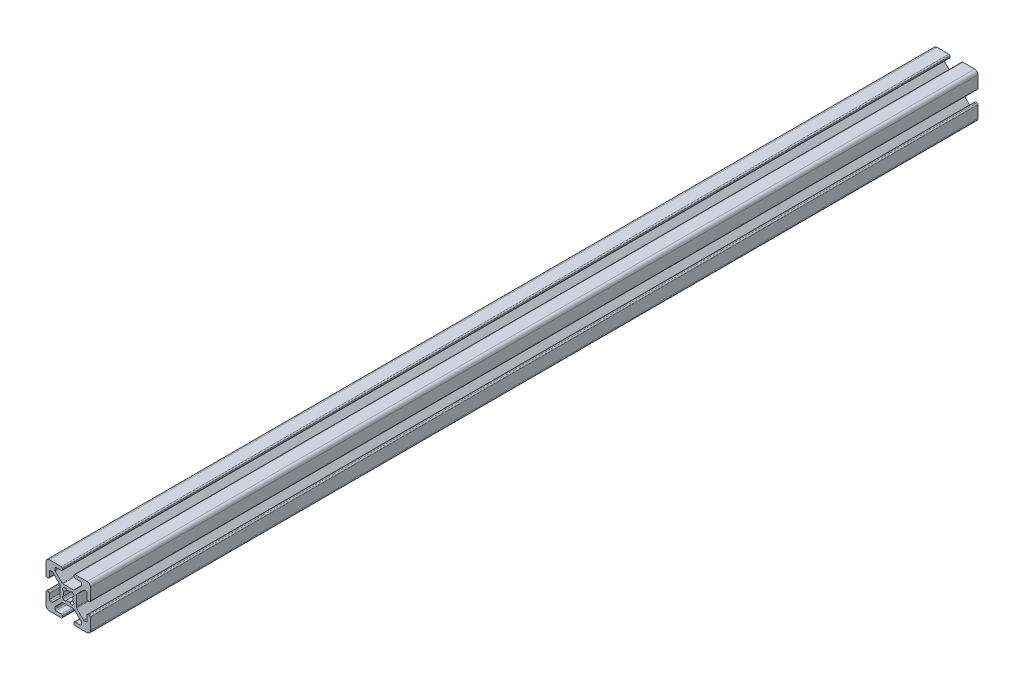
SolidWorks part; units mm, degrees
ref_plane "Front Plane" through (0, 0, 0) normal (0, 0, 1) x (1, 0, 0)
ref_plane "Top Plane" through (0, 0, 0) normal (0, 1, 0) x (1, 0, 0)
ref_plane "Right Plane" through (0, 0, 0) normal (1, 0, 0) x (0, 0, -1)
sketch "Sketch1" plane through (0, 0, 0) normal (0, 0, 1) x (1, 0, 0)
  line L0 (-5.0323, -0.3411) -> (-5.5163, -0.3411)
  line L1 (-6.0243, 0.1669) -> (-6.0243, 2.5159)
  line L2 (-4.5243, 0.1669) -> (-4.5243, 5.5289)
  line L3 (-10.8693, -5.355) -> (-10.8693, -0.5871)
  line L4 (-7.2582, 3.0239) -> (-6.5323, 3.0239)
  line L5 (-7.6174, 2.8752) -> (-10.7205, -0.2279)
  line L6 (-5.0323, -5.6011) -> (-5.5163, -5.6011)
  line L7 (-4.5243, -6.1091) -> (-4.5243, -11.4711)
  line L8 (-6.0243, -6.1091) -> (-6.0243, -8.4581)
  line L9 (-7.2582, -8.9661) -> (-6.5323, -8.9661)
  line L10 (-7.6174, -8.8173) -> (-10.7205, -5.7142)
  line L11 (-12.3994, -5.2756) -> (-12.2198, -5.096)
  line L12 (-17.1543, 6.5209) -> (-17.1543, 6.0369)
  line L13 (-17.6623, 7.0289) -> (-23.0243, 7.0289)
  line L14 (-17.6623, 5.5289) -> (-20.0113, 5.5289)
  line L15 (-12.1404, 0.6839) -> (-16.9082, 0.6839)
  line L16 (-20.5193, 4.295) -> (-20.5193, 5.0209)
  line L17 (-20.3705, 3.9358) -> (-17.2674, 0.8327)
  line L18 (-11.8943, 6.5209) -> (-11.8943, 6.0369)
  line L19 (-11.3863, 7.0289) -> (-6.0243, 7.0289)
  line L20 (-11.3863, 5.5289) -> (-9.0373, 5.5289)
  line L21 (-8.5293, 4.295) -> (-8.5293, 5.0209)
  line L22 (-8.6781, 3.9358) -> (-11.7812, 0.8327)
  line L23 (-12.2198, -0.8462) -> (-12.3994, -0.6666)
  line L24 (-24.0163, -5.6011) -> (-23.5323, -5.6011)
  line L25 (-24.5243, -6.1091) -> (-24.5243, -11.4711)
  line L26 (-23.0243, -6.1091) -> (-23.0243, -8.4581)
  line L27 (-18.1793, -0.5871) -> (-18.1793, -5.355)
  line L28 (-21.7904, -8.9661) -> (-22.5163, -8.9661)
  line L29 (-21.4312, -8.8173) -> (-18.3281, -5.7142)
  line L30 (-24.0163, -0.3411) -> (-23.5323, -0.3411)
  line L31 (-24.5243, 0.1669) -> (-24.5243, 5.5289)
  line L32 (-23.0243, 0.1669) -> (-23.0243, 2.5159)
  line L33 (-21.7904, 3.0239) -> (-22.5163, 3.0239)
  line L34 (-21.4312, 2.8752) -> (-18.3281, -0.2279)
  line L35 (-16.6492, -0.6666) -> (-16.8288, -0.8462)
  line L36 (-11.8943, -12.4631) -> (-11.8943, -11.9791)
  line L37 (-11.3863, -12.9711) -> (-6.0243, -12.9711)
  line L38 (-11.3863, -11.4711) -> (-9.0373, -11.4711)
  line L39 (-16.9082, -6.6261) -> (-12.1404, -6.6261)
  line L40 (-8.5293, -10.2371) -> (-8.5293, -10.9631)
  line L41 (-8.6781, -9.8779) -> (-11.7812, -6.7748)
  line L42 (-17.1543, -12.4631) -> (-17.1543, -11.9791)
  line L43 (-17.6623, -12.9711) -> (-23.0243, -12.9711)
  line L44 (-17.6623, -11.4711) -> (-20.0113, -11.4711)
  line L45 (-20.5193, -10.2371) -> (-20.5193, -10.9631)
  line L46 (-20.3705, -9.8779) -> (-17.2674, -6.7748)
  line L47 (-16.8288, -5.096) -> (-16.6492, -5.2756)
  arc A0 (-15.3283, -4.9062) -> (-13.7203, -4.9062) centre (-14.5243, -2.9711) ccw
  arc A1 (-6.0243, 2.5159) -> (-6.5323, 3.0239) centre (-6.5323, 2.5159) ccw
  arc A2 (-7.2582, 3.0239) -> (-7.6174, 2.8752) centre (-7.2582, 2.5159) ccw
  arc A3 (-10.7205, -0.2279) -> (-10.8693, -0.5871) centre (-10.3613, -0.5871) ccw
  arc A4 (-10.8693, -5.355) -> (-10.7205, -5.7142) centre (-10.3613, -5.355) ccw
  arc A5 (-7.6174, -8.8173) -> (-7.2582, -8.9661) centre (-7.2582, -8.4581) ccw
  arc A6 (-6.5323, -8.9661) -> (-6.0243, -8.4581) centre (-6.5323, -8.4581) ccw
  arc A7 (-5.5163, -5.6011) -> (-6.0243, -6.1091) centre (-5.5163, -6.1091) ccw
  arc A8 (-4.5243, -6.1091) -> (-5.0323, -5.6011) centre (-5.0323, -6.1091) ccw
  arc A9 (-5.0323, -0.3411) -> (-4.5243, 0.1669) centre (-5.0323, 0.1669) ccw
  arc A10 (-6.0243, 0.1669) -> (-5.5163, -0.3411) centre (-5.5163, 0.1669) ccw
  arc A11 (-13.7203, -4.9062) -> (-12.3994, -5.2756) centre (-12.9559, -4.7191) ccw
  arc A12 (-12.2198, -5.096) -> (-12.5892, -3.775) centre (-12.7763, -4.5395) ccw
  arc A13 (-17.1543, 6.5209) -> (-17.6623, 7.0289) centre (-17.6623, 6.5209) ccw
  arc A14 (-17.6623, 5.5289) -> (-17.1543, 6.0369) centre (-17.6623, 6.0369) ccw
  arc A15 (-12.5892, -3.775) -> (-12.5892, -2.1671) centre (-14.5243, -2.9711) ccw
  arc A16 (-17.2674, 0.8327) -> (-16.9082, 0.6839) centre (-16.9082, 1.1919) ccw
  arc A17 (-20.0113, 5.5289) -> (-20.5193, 5.0209) centre (-20.0113, 5.0209) ccw
  arc A18 (-20.5193, 4.295) -> (-20.3705, 3.9358) centre (-20.0113, 4.295) ccw
  arc A19 (-11.8943, 6.0369) -> (-11.3863, 5.5289) centre (-11.3863, 6.0369) ccw
  arc A20 (-11.3863, 7.0289) -> (-11.8943, 6.5209) centre (-11.3863, 6.5209) ccw
  arc A21 (-8.5293, 5.0209) -> (-9.0373, 5.5289) centre (-9.0373, 5.0209) ccw
  arc A22 (-8.6781, 3.9358) -> (-8.5293, 4.295) centre (-9.0373, 4.295) ccw
  arc A23 (-12.1404, 0.6839) -> (-11.7812, 0.8327) centre (-12.1404, 1.1919) ccw
  arc A24 (-12.5892, -2.1671) -> (-12.2198, -0.8462) centre (-12.7763, -1.4027) ccw
  arc A25 (-12.3994, -0.6666) -> (-13.7203, -1.0359) centre (-12.9559, -1.223) ccw
  arc A26 (-24.0163, -5.6011) -> (-24.5243, -6.1091) centre (-24.0163, -6.1091) ccw
  arc A27 (-23.0243, -6.1091) -> (-23.5323, -5.6011) centre (-23.5323, -6.1091) ccw
  arc A28 (-13.7203, -1.0359) -> (-15.3283, -1.0359) centre (-14.5243, -2.9711) ccw
  arc A29 (-18.3281, -5.7142) -> (-18.1793, -5.355) centre (-18.6873, -5.355) ccw
  arc A30 (-23.0243, -8.4581) -> (-22.5163, -8.9661) centre (-22.5163, -8.4581) ccw
  arc A31 (-21.7904, -8.9661) -> (-21.4312, -8.8173) centre (-21.7904, -8.4581) ccw
  arc A32 (-23.5323, -0.3411) -> (-23.0243, 0.1669) centre (-23.5323, 0.1669) ccw
  arc A33 (-24.5243, 0.1669) -> (-24.0163, -0.3411) centre (-24.0163, 0.1669) ccw
  arc A34 (-22.5163, 3.0239) -> (-23.0243, 2.5159) centre (-22.5163, 2.5159) ccw
  arc A35 (-21.4312, 2.8752) -> (-21.7904, 3.0239) centre (-21.7904, 2.5159) ccw
  arc A36 (-18.1793, -0.5871) -> (-18.3281, -0.2279) centre (-18.6873, -0.5871) ccw
  arc A37 (-15.3283, -1.0359) -> (-16.6492, -0.6666) centre (-16.0927, -1.223) ccw
  arc A38 (-16.8288, -0.8462) -> (-16.4594, -2.1671) centre (-16.2723, -1.4027) ccw
  arc A39 (-11.8943, -12.4631) -> (-11.3863, -12.9711) centre (-11.3863, -12.4631) ccw
  arc A40 (-11.3863, -11.4711) -> (-11.8943, -11.9791) centre (-11.3863, -11.9791) ccw
  arc A41 (-16.4594, -2.1671) -> (-16.4594, -3.775) centre (-14.5243, -2.9711) ccw
  arc A42 (-11.7812, -6.7748) -> (-12.1404, -6.6261) centre (-12.1404, -7.1341) ccw
  arc A43 (-9.0373, -11.4711) -> (-8.5293, -10.9631) centre (-9.0373, -10.9631) ccw
  arc A44 (-8.5293, -10.2371) -> (-8.6781, -9.8779) centre (-9.0373, -10.2371) ccw
  arc A45 (-17.1543, -11.9791) -> (-17.6623, -11.4711) centre (-17.6623, -11.9791) ccw
  arc A46 (-17.6623, -12.9711) -> (-17.1543, -12.4631) centre (-17.6623, -12.4631) ccw
  arc A47 (-20.5193, -10.9631) -> (-20.0113, -11.4711) centre (-20.0113, -10.9631) ccw
  arc A48 (-20.3705, -9.8779) -> (-20.5193, -10.2371) centre (-20.0113, -10.2371) ccw
  arc A49 (-16.9082, -6.6261) -> (-17.2674, -6.7748) centre (-16.9082, -7.1341) ccw
  arc A50 (-16.4594, -3.775) -> (-16.8288, -5.096) centre (-16.2723, -4.5395) ccw
  arc A51 (-16.6492, -5.2756) -> (-15.3283, -4.9062) centre (-16.0927, -4.7191) ccw
  arc A52 (-4.5243, 5.5289) -> (-6.0243, 7.0289) centre (-6.0243, 5.5289) ccw
  arc A53 (-6.0243, -12.9711) -> (-4.5243, -11.4711) centre (-6.0243, -11.4711) ccw
  arc A54 (-24.5243, -11.4711) -> (-23.0243, -12.9711) centre (-23.0243, -11.4711) ccw
  arc A55 (-23.0243, 7.0289) -> (-24.5243, 5.5289) centre (-23.0243, 5.5289) ccw
extrude "Extrude1" add sketch "Sketch1" along normal blind 400
